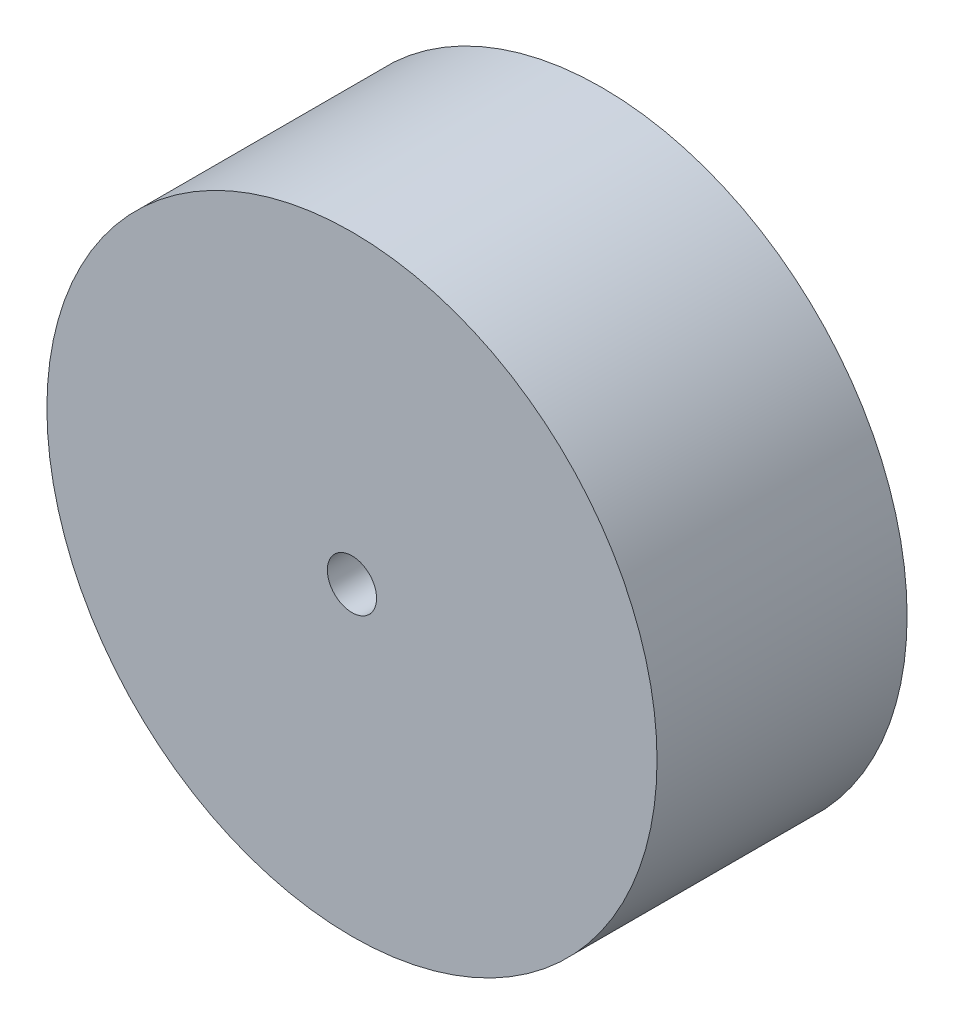
SolidWorks part; units mm, degrees
ref_plane "Front Plane" through (0, 0, 0) normal (0, 0, 1) x (1, 0, 0)
ref_plane "Top Plane" through (0, 0, 0) normal (0, 1, 0) x (1, 0, 0)
ref_plane "Right Plane" through (0, 0, 0) normal (1, 0, 0) x (0, 0, -1)
sketch "Sketch1" plane through (0, 0, 0) normal (0, 0, 1) x (1, 0, 0)
  circle A0 centre (0, 0) radius 30.988
  circle A1 centre (0, 0) radius 2.5
  dimension "D1" = 61.976
  dimension "D2" = 5
extrude "Boss-Extrude1" add sketch "Sketch1" along normal blind 25.4
